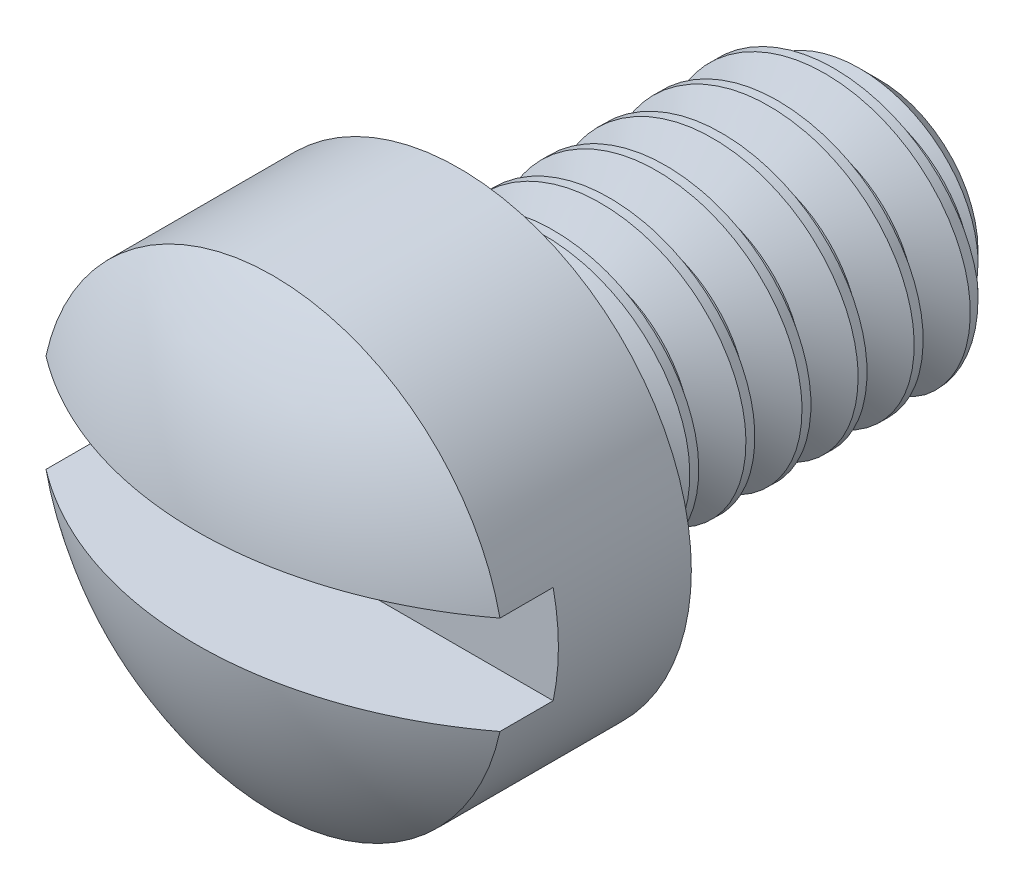
SolidWorks part; units mm, degrees
ref_plane "Front" through (0, 0, 0) normal (0, 0, 1) x (1, 0, 0)
ref_plane "Top" through (0, 0, 0) normal (0, 1, 0) x (1, 0, 0)
ref_plane "Right" through (0, 0, 0) normal (1, 0, 0) x (0, 0, -1)
sketch "Sketch1" plane through (0, 0, 0) normal (0, 0, 1) x (1, 0, 0)
  circle A0 centre (0, 0) radius 5.2578
  dimension "Head Dia" = 10.5156
extrude "Extrude3" add sketch "Sketch1" along normal blind 6.0198
sketch "Sketch11" plane through (0, 0, 0) normal (1, 0, 0) x (0, 0, -1)
  line L0 (0, 0) -> (-6.2738, 0) construction
  line L4 (-6.0198, 5.2578) -> (-6.0198, -5.2578) construction
  line L5 (-6.2738, 5.4681) -> (0, 5.4681)
  line L7 (0, 5.4681) -> (0, 5.2578)
  line L8 (-4.2139, 5.2578) -> (0, 5.2578)
  line L9 (0, -5.2578) -> (0, 5.2578) construction
  line L13 (-6.0198, 0) -> (-6.2738, 0)
  line L14 (-6.2738, 0) -> (-6.2738, 5.4681)
  arc A0 (-4.2139, 5.2578) -> (-6.0198, 0) centre (2.5369, 0) ccw
  dimension "D3" = 0.254
  dimension "D5" = 0.2103
  dimension "D2" = 1.8059
revolve "Cut-Revolve3" cut sketch "Sketch11" angle 360 about L0
sketch "Sketch4" plane through (0, 0, 0) normal (1, 0, 0) x (0, 0, -1)
  line L0 (0, 0) -> (9.525, 0)
  line L3 (9.525, 0) -> (9.525, 3.175)
  line L4 (9.525, 3.175) -> (0, 3.175)
  line L6 (0, 3.175) -> (0, 0)
  line L9 (9.525, 3.175) -> (9.525, -3.175) construction
  dimension "length" = 9.525
  dimension "dia" = 6.35
revolve "Revolve1" add sketch "Sketch4" angle 360 about L0
sketch "Sketch13" plane through (0, 0, -9.525) normal (0, 0, -1) x (-1, 0, 0)
  circle A2 centre (0, 0) radius 3.175
curve "Helix/Spiral1" pitch 1.27 height 15.5448 radius 3.175 centre (0, 0, -9.525) axis (0, 0, 1) start towards (1, 0, 0)
chamfer "Chamfer2" distance 0.9525 angle 45 1 edges at (3.175, 0, -9.525)
sketch "Sketch14" plane through (0, 0, 0) normal (1, 0, 0) x (0, 0, -1)
  line L0 (9.525, 3.2147) -> (10.6363, 3.2147)
  line L1 (10.6363, 3.2147) -> (10.16, 2.3555)
  line L2 (10.16, 2.3555) -> (10.0012, 2.3555)
  line L3 (10.0012, 2.3555) -> (9.525, 3.2147)
  line L4 (9.7631, 2.7851) -> (10.3981, 2.7851) construction
  dimension "D1" = 0.1588
  dimension "D2" = 58
  dimension "D3" = 0.635
  dimension "D4" = 0.0397
sweep "Cut-Sweep1" cut profiles "Sketch14" path "Helix/Spiral1" align with end faces yes
ref_plane "Plane1" through (0, 0, 28.575) normal (0, 0, -1) x (-1, 0, 0)
sketch "Sketch29" [suppressed] plane through (0, 0, 28.575) normal (0, 0, -1) x (-1, 0, 0)
  circle A0 centre (0, 0) radius 1.7526 construction
  circle A1 centre (0, 0) radius 1.7526
  point P3 (0, -1.7526)
  point P4 (0, 1.7526)
extrude "Extrude11" [suppressed] add sketch "Sketch29" against normal up to surface (28.575 mm away) up to plane "Front"
ref_plane "Plane2" through (0, 0, 6.0198) normal (0, 0, 1) x (1, 0, 0)
sketch "Sketch26" plane through (0, 0, 0) normal (0, 0, 1) x (1, 0, 0)
  circle A1 centre (0, 0) radius 0.5461
  dimension "D1" = 1.0922
extrude "Extrude13" add sketch "Sketch26" along normal up to surface (6.0024 mm away)
sketch "Sketch31" plane through (0, 0, 6.0198) normal (0, 0, 1) x (1, 0, 0)
  line L0 (-5.2578, 1.1113) -> (5.2578, -1.1112) construction
  line L1 (-5.2578, 1.1113) -> (5.2578, 1.1113)
  line L2 (-5.2578, 1.1113) -> (-5.2578, -1.1113)
  line L3 (-5.2578, -1.1113) -> (5.2578, -1.1112)
  line L4 (5.2578, 1.1113) -> (5.2578, -1.1112)
  circle A0 centre (0, 0) radius 5.2578 construction
  dimension "D1" = 2.2225
extrude "Extrude15" cut sketch "Sketch31" against normal blind 3.0099
sketch "Sketch18" plane through (0, 0, 0) normal (1, 0, 0) x (0, 0, -1)
  line L1 (9.525, 3.175) -> (0, 3.175) construction
  point P0 (7.62, -3.175)
  point P1 (8.255, 3.175)
  point P2 (-6.0198, 1.1113)
  dimension "D1" = 1.27
  dimension "D2" = 1.905
equation "\"D3@Helix/Spiral1\" = \"length@Sketch4\" + \"Head Ht@Extrude3\""
equation "\"D1@Sketch14\" = \"D4@Helix/Spiral1\" * .125"
equation "\"D3@Sketch14\" = \"D4@Helix/Spiral1\" * .5"
equation "\"D5@Sketch11\" = \"Head Dia@Sketch1\" * .02"
equation "\"D4@Sketch14\" = \"D1@Sketch14\" * .25"
equation "\"D1@Chamfer2\" = \"D4@Helix/Spiral1\" * .75"
equation "\"D1@Sketch18\" = \"D4@Helix/Spiral1\""
equation "\"D2@Sketch18\" = \"D4@Helix/Spiral1\" * 1.5"
equation "\"D1@Extrude15\" = \"Head Ht@Extrude3\" * .5"
equation "\"D2@Sketch11\" = \"Head Ht@Extrude3\" * .3"
equation "\"D1@Sketch31\" = \"D4@Helix/Spiral1\" * 1.75"
